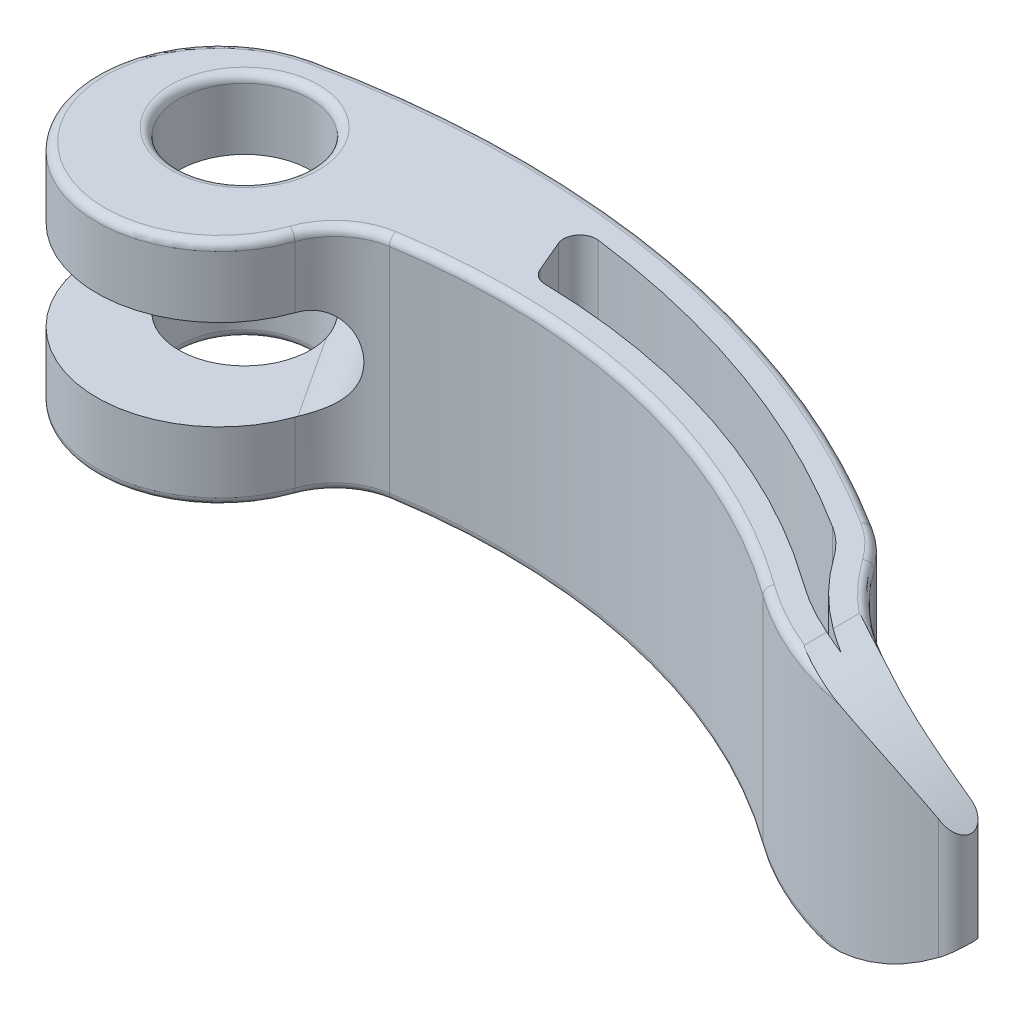
SolidWorks part; units mm, degrees
ref_plane "前视基准面" through (0, 0, 0) normal (0, 0, 1) x (1, 0, 0)
ref_plane "上视基准面" through (0, 0, 0) normal (0, 1, 0) x (1, 0, 0)
ref_plane "右视基准面" through (0, 0, 0) normal (1, 0, 0) x (0, 0, -1)
sketch "Sketch1" plane through (0, 0, 0) normal (0, 1, 0) x (1, 0, 0)
  line L0 (0, 0) -> (0, -1.52) construction
  line L1 (0, -4) -> (7.0569, -4) construction
  circle A0 centre (0, 0) radius 4
  circle A1 centre (0, -1.52) radius 7.48 construction
  circle A2 centre (54.25, -11) radius 1 construction
  arc A3 (-1.5362, 5.8005) -> (39.9138, -1.6868) centre (9.965, -49.0057) cw
  arc A4 (39.9138, -1.6868) -> (42.0185, -3.6828) centre (35.9028, -8.0242) cw
  arc A5 (42.0185, -3.6828) -> (54.25, -10) centre (54.25, 5) ccw
  arc A6 (7.0569, -4) -> (10.1902, -1.3778) centre (10.8307, -5.3262) cw
  arc A7 (10.1902, -1.3778) -> (39.9668, -8.4001) centre (16.5949, -40.8617) cw
  arc A8 (39.9668, -8.4001) -> (54.25, -12) centre (51.6528, 7.8306) ccw
  arc A9 (-1.5362, 5.8005) -> (7.0569, -4) centre (0, -1.52) ccw
  arc A10 (54.25, -10) -> (54.25, -12) centre (54.25, -11) cw
  dimension "D1" = 8
  dimension "D3" = 14.96
  dimension "D4" = 2
  dimension "D7" = 56
  dimension "D8" = 7.5
  dimension "D9" = 15
  dimension "D11" = 4
  dimension "D12" = 40
  dimension "D13" = 20
  dimension "D2" = 1.52
  dimension "D5" = 54.25
  dimension "D6" = 11
  dimension "D10" = 41.45
extrude "Boss-Extrude1" add sketch "Sketch1" along normal mid plane 14
sketch "Sketch3" plane through (0, 7, 0) normal (0, 1, 0) x (1, 0, 0)
  line L0 (15, 5.0102) -> (16.75, 0.888)
  arc A16 (-1.1768, 4.0879) -> (5.4059, -3.4198) centre (0, -1.52) ccw
  arc A17 (9.91, 0.3496) -> (5.4059, -3.4198) centre (10.8307, -5.3262) ccw
  arc A18 (40.9893, -6.98) -> (9.91, 0.3496) centre (16.5949, -40.8617) ccw
  arc A19 (40.9893, -6.98) -> (45.7717, -9.4458) centre (51.6528, 7.8306) ccw
  arc A20 (40.5915, -4.6958) -> (45.7717, -9.4458) centre (54.25, 5) ccw
  arc A21 (40.5915, -4.6958) -> (38.9779, -3.1655) centre (35.9028, -8.0242) ccw
  arc A22 (38.9779, -3.1655) -> (-1.1768, 4.0879) centre (9.965, -49.0057) ccw
  arc A23 (-1.1768, 4.0879) -> (5.4059, -3.4198) centre (0, -1.52) ccw
  arc A24 (9.91, 0.3496) -> (5.4059, -3.4198) centre (10.8307, -5.3262) ccw
  arc A25 (40.9893, -6.98) -> (9.91, 0.3496) centre (16.5949, -40.8617) ccw
  arc A26 (40.9893, -6.98) -> (45.7717, -9.4458) centre (51.6528, 7.8306) ccw
  arc A27 (40.5915, -4.6958) -> (45.7717, -9.4458) centre (54.25, 5) ccw
  arc A28 (40.5915, -4.6958) -> (38.9779, -3.1655) centre (35.9028, -8.0242) ccw
  arc A29 (38.9779, -3.1655) -> (-1.1768, 4.0879) centre (9.965, -49.0057) ccw
  dimension "D2" = 16.75
  dimension "D3" = 15
  dimension "D1" = 1.75
extrude "Cut-Extrude1" cut sketch "Sketch3" against normal through all contours A28 A29 L0 A25 A26 A27 region at (27.9201, 7, 0.0093)
fillet "Fillet1" radius 1 2 edges at (15, 0, -5.0102) (16.75, 0, -0.888) tangent propagation no
sketch "Sketch4" plane through (0, 0, 0) normal (0, 1, 0) x (1, 0, 0)
  line L0 (0, 0) -> (0, 12) construction
  line L1 (0, 0) -> (-18.3, 0) construction
  line L2 (0, 12) -> (-18.3, 0)
  line L3 (0, 12) -> (12, -6.3)
  line L4 (-18.3, 0) -> (-6.3, -18.3)
  line L5 (12, -6.3) -> (-6.3, -18.3)
  dimension "D1" = 12
  dimension "D2" = 18.3
extrude "Cut-Extrude2" cut sketch "Sketch4" against normal mid plane 5.5
fillet "Fillet2" 2 edges at (6.274, -2.75, -2.4322) (6.274, 2.75, -2.4322) type full round first side face at (0, -2.75, -4) second side face at (0, 2.75, -4) middle face at (6.274, 0, -2.4322)
sketch "Sketch5" plane through (0, 0, 0) normal (0, 0, 1) x (1, 0, 0)
  line L0 (0, 0) -> (58, 0) construction
  line L1 (54.25, 7) -> (39.9668, 7) construction
  arc A0 (58, 0) -> (44.35, 7) centre (43.9007, -10.6848) ccw
  arc A1 (58, 0) -> (44.35, -7) centre (43.9007, 10.6848) cw
  dimension "D1" = 58
  dimension "D2" = 13.65
extrude "Cut-Extrude4" cut sketch "Sketch5" against normal through all both and the other way through all
fillet "Fillet5" radius 0.5 16 edges at (43.109, -7, 5.0438) (41.0635, -7, 2.5821) (42.0836, -7, 9.7316) (25.7764, -7, 1.9297) (8.2635, -7, 2.2587) (-5.6242, -7, 6.4514) (43.109, 7, 5.0438) (41.0635, 7, 2.5821) (19.9195, 7, -6.1025) (42.0836, 7, 9.7316) (25.7764, 7, 1.9297) (8.2635, 7, 2.2587) (0, -7, 4) (19.9195, -7, -6.1025) (-5.6242, 7, 6.4514) (0, 7, 4)
